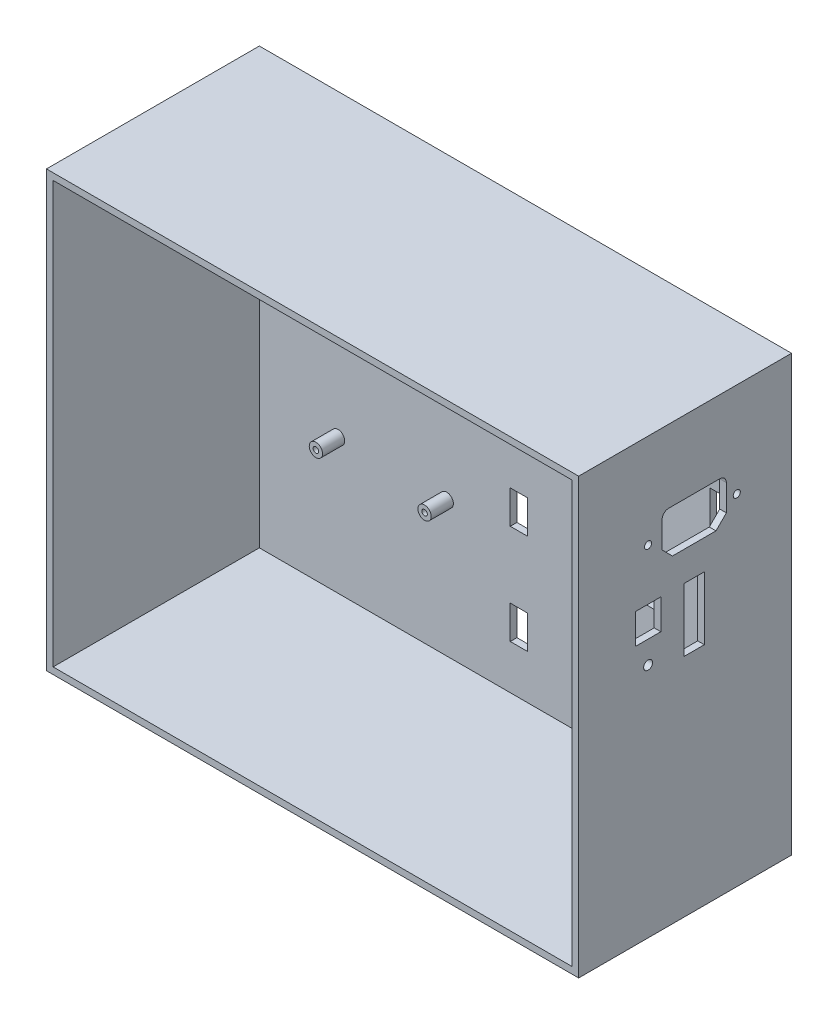
SolidWorks part; units mm, degrees
ref_plane "Front Plane" through (0, 0, 0) normal (0, 0, 1) x (1, 0, 0)
ref_plane "Top Plane" through (0, 0, 0) normal (0, 1, 0) x (1, 0, 0)
ref_plane "Right Plane" through (0, 0, 0) normal (1, 0, 0) x (0, 0, -1)
sketch "Sketch1" plane through (0, 0, 0) normal (0, 0, 1) x (1, 0, 0)
  line L1 (117, 95) -> (-117, 95)
  line L2 (117, 95) -> (117, -95)
  line L3 (117, -95) -> (-117, -95)
  line L4 (-117, 95) -> (-117, -95)
  line L5 (117, 95) -> (-117, -95) construction
  line L6 (117, -95) -> (-117, 95) construction
  point P0 (0, 0)
  dimension "D1" = 234
  dimension "D2" = 190
extrude "Boss-Extrude1" add sketch "Sketch1" along normal blind 3
sketch "Sketch2" plane through (0, 0, 3) normal (0, 0, 1) x (1, 0, 0)
  line L4 (-117, 95) -> (-117, -95)
  line L5 (-117, -95) -> (117, -95)
  line L6 (117, -95) -> (117, 95)
  line L7 (117, 95) -> (-117, 95)
  line L8 (-117, 95) -> (-117, -95)
  line L9 (-117, -95) -> (117, -95)
  line L10 (117, -95) -> (117, 95)
  line L11 (117, 95) -> (-117, 95)
  dimension "D1" = 0
extrude "Extrude-Thin1" add sketch "Sketch2" along normal blind 93 and the other way blind 3 thin thin type one direction wall 3
sketch "Sketch3" plane through (0, 0, 0) normal (0, 0, -1) x (-1, 0, 0)
  line L0 (-120, 0) -> (120, 0) construction
  line L1 (-120, -98) -> (-120, 98) construction
  line L2 (120, 98) -> (120, -98) construction
  line L3 (-56.15, 30) -> (-56.15, 15)
  line L4 (-93.85, 30) -> (-86.15, 30)
  line L5 (-93.85, 30) -> (-93.85, 15)
  line L6 (-93.85, 15) -> (-86.15, 15)
  line L7 (-86.15, 30) -> (-86.15, 15)
  line L8 (-93.85, 30) -> (-86.15, 15) construction
  line L9 (-93.85, 15) -> (-86.15, 30) construction
  line L10 (-63.85, 15) -> (-56.15, 15)
  line L11 (-63.85, 30) -> (-63.85, 15)
  line L12 (-63.85, 30) -> (-56.15, 30)
  line L13 (-26.15, 30) -> (-26.15, 15)
  line L14 (-33.85, 15) -> (-26.15, 15)
  line L15 (-33.85, 30) -> (-33.85, 15)
  line L16 (-33.85, 30) -> (-26.15, 30)
  line L17 (3.85, 30) -> (3.85, 15)
  line L18 (-3.85, 15) -> (3.85, 15)
  line L19 (-3.85, 30) -> (-3.85, 15)
  line L20 (-3.85, 30) -> (3.85, 30)
  line L21 (-56.15, 75) -> (-56.15, 60)
  line L22 (-63.85, 60) -> (-56.15, 60)
  line L23 (-63.85, 75) -> (-63.85, 60)
  line L24 (-63.85, 75) -> (-56.15, 75)
  line L25 (-26.15, 75) -> (-26.15, 60)
  line L26 (-33.85, 60) -> (-26.15, 60)
  line L27 (-33.85, 75) -> (-33.85, 60)
  line L28 (-33.85, 75) -> (-26.15, 75)
  line L29 (3.85, 75) -> (3.85, 60)
  line L30 (-3.85, 60) -> (3.85, 60)
  line L31 (-3.85, 75) -> (-3.85, 60)
  line L32 (-3.85, 75) -> (3.85, 75)
  line L33 (-86.15, 75) -> (-86.15, 60)
  line L34 (-93.85, 60) -> (-86.15, 60)
  line L35 (-93.85, 75) -> (-93.85, 60)
  line L36 (-93.85, 75) -> (-86.15, 75)
  line L37 (-93.85, -15) -> (-86.15, -30) construction
  line L38 (-93.85, -30) -> (-86.15, -15) construction
  line L39 (-93.85, -75) -> (-86.15, -75)
  line L40 (-93.85, -75) -> (-93.85, -60)
  line L41 (-93.85, -60) -> (-86.15, -60)
  line L42 (-86.15, -75) -> (-86.15, -60)
  line L43 (-3.85, -75) -> (3.85, -75)
  line L44 (-3.85, -75) -> (-3.85, -60)
  line L45 (-3.85, -60) -> (3.85, -60)
  line L46 (3.85, -75) -> (3.85, -60)
  line L47 (-33.85, -75) -> (-26.15, -75)
  line L48 (-33.85, -75) -> (-33.85, -60)
  line L49 (-33.85, -60) -> (-26.15, -60)
  line L50 (-26.15, -75) -> (-26.15, -60)
  line L51 (-63.85, -75) -> (-56.15, -75)
  line L52 (-63.85, -75) -> (-63.85, -60)
  line L53 (-63.85, -60) -> (-56.15, -60)
  line L54 (-56.15, -75) -> (-56.15, -60)
  line L55 (-3.85, -30) -> (3.85, -30)
  line L56 (-3.85, -30) -> (-3.85, -15)
  line L57 (-3.85, -15) -> (3.85, -15)
  line L58 (3.85, -30) -> (3.85, -15)
  line L59 (-33.85, -30) -> (-26.15, -30)
  line L60 (-33.85, -30) -> (-33.85, -15)
  line L61 (-33.85, -15) -> (-26.15, -15)
  line L62 (-26.15, -30) -> (-26.15, -15)
  line L63 (-63.85, -30) -> (-56.15, -30)
  line L64 (-63.85, -30) -> (-63.85, -15)
  line L65 (-63.85, -15) -> (-56.15, -15)
  line L66 (-86.15, -30) -> (-86.15, -15)
  line L67 (-93.85, -15) -> (-86.15, -15)
  line L68 (-93.85, -30) -> (-93.85, -15)
  line L69 (-93.85, -30) -> (-86.15, -30)
  line L70 (-56.15, -30) -> (-56.15, -15)
  point P6 (-90, 22.5)
  point P71 (-90, -22.5)
  dimension "D1" = 45
  dimension "D2" = 15
  dimension "D3" = 7.7
  dimension "D4" = 30
  dimension "D5" = 4
  dimension "D6" = 2
extrude "Cut-Extrude1" cut sketch "Sketch3" against normal up to surface (3 mm away) up to face at (0, 0, 3)
sketch "Sketch4" plane through (120, 0, 0) normal (1, 0, 0) x (0, 0, -1)
  line L0 (-43.8814, 81.0619) -> (-43.8814, -10.9381) construction
  line L1 (-9.8493, 55.4182) -> (-77.9135, 55.4182) construction
  line L2 (-53.6951, 45.6682) -> (-58.3814, 50.3545)
  line L3 (-32.3814, 65.1682) -> (-55.3814, 65.1682)
  line L4 (-29.3814, 62.1682) -> (-29.3814, 50.3545)
  line L5 (-34.0678, 45.6682) -> (-53.6951, 45.6682)
  line L6 (-58.3814, 62.1682) -> (-58.3814, 50.3545)
  line L7 (-29.3814, 65.1682) -> (-58.3814, 45.6682) construction
  line L8 (-29.3814, 45.6682) -> (-58.3814, 65.1682) construction
  line L9 (-29.3814, 50.3545) -> (-34.0678, 45.6682)
  line L10 (-39.3224, 32.317) -> (-48.4404, 32.317)
  line L11 (-39.3224, 32.317) -> (-39.3224, 3.8231)
  line L12 (-39.3224, 3.8231) -> (-48.4404, 3.8231)
  line L13 (-48.4404, 32.317) -> (-48.4404, 3.8231)
  line L14 (-39.3224, 32.317) -> (-48.4404, 3.8231) construction
  line L15 (-39.3224, 3.8231) -> (-48.4404, 32.317) construction
  line L16 (-58.9377, 32.317) -> (-70.4344, 32.317)
  line L17 (-58.9377, 32.317) -> (-58.9377, 18.7069)
  line L18 (-58.9377, 18.7069) -> (-70.4344, 18.7069)
  line L19 (-70.4344, 32.317) -> (-70.4344, 18.7069)
  line L20 (-58.9377, 32.317) -> (-70.4344, 18.7069) construction
  line L21 (-58.9377, 18.7069) -> (-70.4344, 32.317) construction
  circle A0 centre (-64.686, 55.4182) radius 1.6
  circle A1 centre (-24.686, 55.4182) radius 1.6
  arc A2 (-32.3814, 65.1682) -> (-29.3814, 62.1682) centre (-32.3814, 62.1682) cw
  arc A3 (-55.3814, 65.1682) -> (-58.3814, 62.1682) centre (-55.3814, 62.1682) ccw
  circle A4 centre (-64.686, 8.5619) radius 2
  point P5 (-43.8814, 55.4182)
  point P9 (-43.8814, 55.4182)
  point P24 (-43.8814, 18.07)
  point P29 (-64.686, 25.5119)
  point P36 (0, 0)
  point P37 (-29.3814, 50.3545)
  point P38 (-43.8814, 45.6682)
  point P39 (0, 0)
extrude "Cut-Extrude2" cut sketch "Sketch4" against normal up to surface (3 mm away) up to face at (117, 0, 49.5)
sketch "Sketch5" plane through (0, 0, 3) normal (0, 0, 1) x (1, 0, 0)
  line L0 (-117, 95) -> (-117, -95) construction
  line L1 (-32.5, 24) -> (-81.5, 24) construction
  line L2 (-32.5, 24) -> (-32.5, -34) construction
  line L3 (-32.5, -34) -> (-81.5, -34) construction
  line L4 (-81.5, 24) -> (-81.5, -34) construction
  line L5 (-32.5, 24) -> (-81.5, -34) construction
  line L6 (-32.5, -34) -> (-81.5, 24) construction
  line L7 (117, 95) -> (-117, 95) construction
  circle A0 centre (-81.5, 24) radius 1.25
  circle A1 centre (-32.5, 24) radius 1.25
  circle A2 centre (-81.5, -34) radius 1.25
  circle A3 centre (-32.5, -34) radius 1.25
  circle A4 centre (-81.5, 24) radius 3
  circle A5 centre (-32.5, 24) radius 3
  circle A6 centre (-81.5, -34) radius 3
  circle A7 centre (-32.5, -34) radius 3
  point P0 (-57, -5)
  dimension "D3" = 2.5
  dimension "D4" = 6
  dimension "D1" = 49
  dimension "D2" = 58
  dimension "D5" = 60
  dimension "D6" = 100
extrude "Boss-Extrude2" add sketch "Sketch5" along normal blind 10
